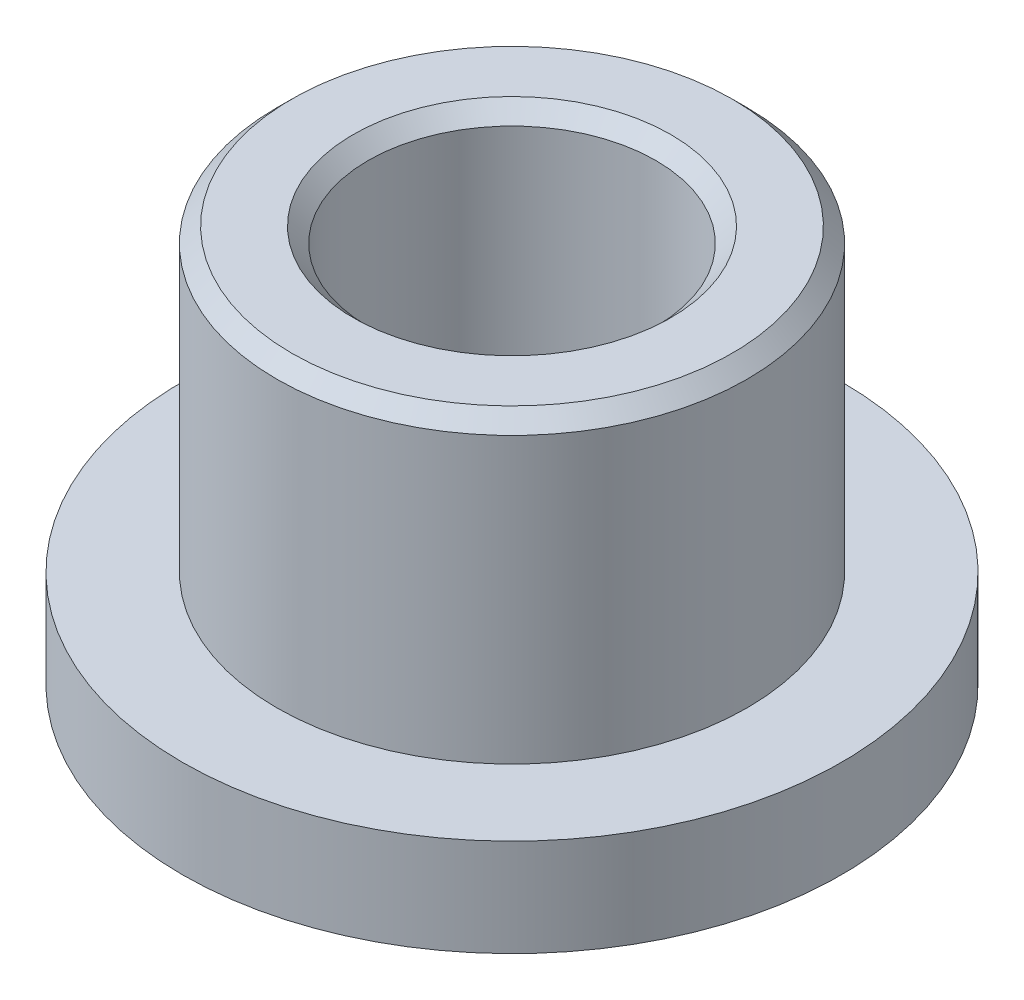
SolidWorks part; units mm, degrees
material "Brass"
ref_plane "Front" through (0, 0, 0) normal (0, 0, 1) x (1, 0, 0)
ref_plane "Top" through (0, 0, 0) normal (0, 1, 0) x (1, 0, 0)
ref_plane "Right" through (0, 0, 0) normal (1, 0, 0) x (0, 0, -1)
ref_axis "side-side" through (80.9, 0, 0) along (-1, 0, 0)
ref_axis "up-down" through (0, 50, 0) along (0, -1, 0)
ref_axis "front-back" through (0, 0, -80.9) along (0, 0, 1)
sketch "Sketch1" plane through (0, 0, 0) normal (0, 0, 1) x (1, 0, 0)
  line L3 (3.925, 1.6256) -> (3.925, 12.4)
  line L7 (5.5, 1.6256) -> (3.925, 1.6256)
  line L11 (5.5, 0) -> (5.5, 1.6256)
  line L15 (3.925, 12.4) -> (2.4, 12.4)
  line L18 (2.4, 0.2) -> (2.4, 12.4)
  line L22 (2.6, 0) -> (2.4, 0.2)
  line L27 (5.5, 0) -> (2.6, 0)
  line L28 (0, 0) -> (0, -3.6079) construction
  dimension "D1" = 1.6256
revolve "Revolve1" add sketch "Sketch1" angle 360 about L28
sketch "Sketch2" plane through (0, 0, 0) normal (0, 0, 1) x (1, 0, 0)
  line L1 (-7, 14.6256) -> (7, 14.6256)
  line L2 (-7, 14.6256) -> (-7, 6.6256)
  line L3 (-7, 6.6256) -> (7, 6.6256)
  line L4 (7, 14.6256) -> (7, 6.6256)
  line L5 (0, 0) -> (0, 6.6256) construction
  line L6 (5.5, 1.6256) -> (-5.5, 1.6256) construction
  dimension "D1" = 5
  dimension "D2" = 14
  dimension "D3" = 8
extrude "Cut-Extrude1" cut sketch "Sketch2" against normal through all both and the other way through all
chamfer "Chamfer1" distance 0.25 angle 45 2 edges at (0, 6.6256, -2.4) (0, 6.6256, -3.925)
